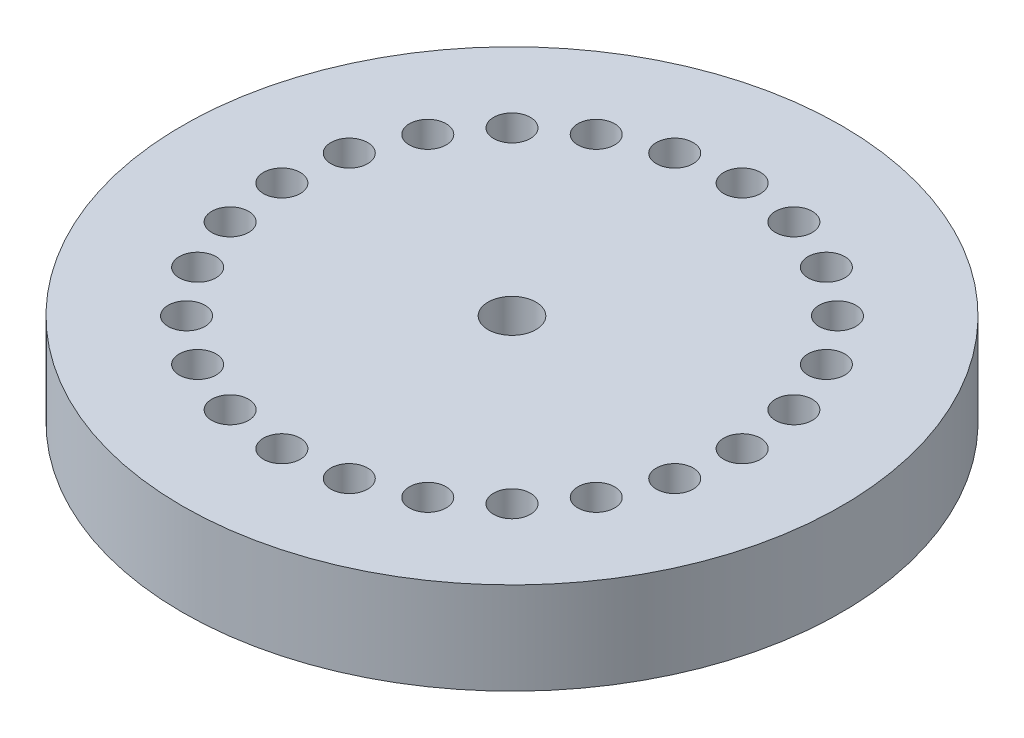
SolidWorks part; units mm, degrees
ref_plane "Front Plane" through (0, 0, 0) normal (0, 0, 1) x (1, 0, 0)
ref_plane "Top Plane" through (0, 0, 0) normal (0, 1, 0) x (1, 0, 0)
ref_plane "Right Plane" through (0, 0, 0) normal (1, 0, 0) x (0, 0, -1)
sketch "Sketch1" plane through (0, 0, 0) normal (0, 1, 0) x (1, 0, 0)
  circle A0 centre (0, 0) radius 20.066 construction
  circle A1 centre (0, 0) radius 45.466
  dimension "D1" = 25.4
extrude "Boss-Extrude1" add sketch "Sketch1" along normal blind 25.4
sketch "Sketch3" plane through (0, 0, 0) normal (0, -1, 0) x (1, 0, 0)
  circle A0 centre (0, 0) radius 20.32
extrude "Cut-Extrude1" cut sketch "Sketch3" against normal blind 12.7
sketch "Sketch4" plane through (0, 0, 0) normal (0, -1, 0) x (1, 0, 0)
  line L0 (0, 0) -> (0, 31.75) construction
  circle A0 centre (0, 31.75) radius 1.778
hole_wizard "CSK for 1/4 Flat Head Machine Screw1" positions "Sketch6" profile "Sketch7" countersink size "1/4" standard "ANSI Inch"
sketch "Sketch6" plane through (0, 25.4, 0) normal (0, 1, 0) x (1, 0, 0)
  point P0 (0, 0)
sketch "Sketch7" plane through (0, 25.4, 0) normal (1, 0, 0) x (0, 0, 1)
  line L0 (0, 0) -> (0, 27.3611)
  line L1 (0, 27.3611) -> (3.2639, 25.4)
  line L2 (3.2639, 25.4) -> (3.2639, 3.6524)
  line L3 (3.2639, 3.6524) -> (6.4389, 0)
  line L5 (6.4389, 0) -> (0, 0)
  line L6 (-3.2639, 3.6524) -> (-6.4389, 0) construction
  line L10 (0, 27.3611) -> (-3.2639, 25.4) construction
  line L11 (0, -6.35) -> (0, 107.95) construction
  dimension "Hole Dia." = 6.5278
  dimension "Hole Depth" = 25.4
  dimension "Near C'Sink Dia." = 12.8778
  dimension "Near C'Sink Angle" = 82
  dimension "Drill Angle" = 118
sketch "Sketch8" plane through (0, 25.4, 0) normal (0, 1, 0) x (1, 0, 0)
  circle A0 centre (0, 0) radius 46.9556
extrude "Cut-Extrude2" cut sketch "Sketch8" against normal blind 12.7
extrude "Cut-Extrude3" cut sketch "Sketch4" against normal through all
sketch "Sketch9" plane through (0, 12.7, 0) normal (0, 1, 0) x (1, 0, 0)
  circle A0 centre (0, -31.75) radius 2.54
extrude "Cut-Extrude4" cut sketch "Sketch9" against normal blind 5.08
pattern_circular "CirPattern1" count 24 every 15 about axis through (0, 12.7, 0) along (0, -1, 0) of "Cut-Extrude3", "Cut-Extrude4"
sketch "Sketch10" plane through (0, 12.7, 0) normal (0, 1, 0) x (1, 0, 0)
  circle A0 centre (0, 0) radius 22.8348
extrude "Boss-Extrude2" add sketch "Sketch10" against normal blind 5.08
sketch "Sketch11" plane through (0, 12.7, 0) normal (0, 1, 0) x (1, 0, 0)
  circle A0 centre (0, 0) radius 3.302
  dimension "D1" = 6.604
extrude "Cut-Extrude5" cut sketch "Sketch11" against normal through all
